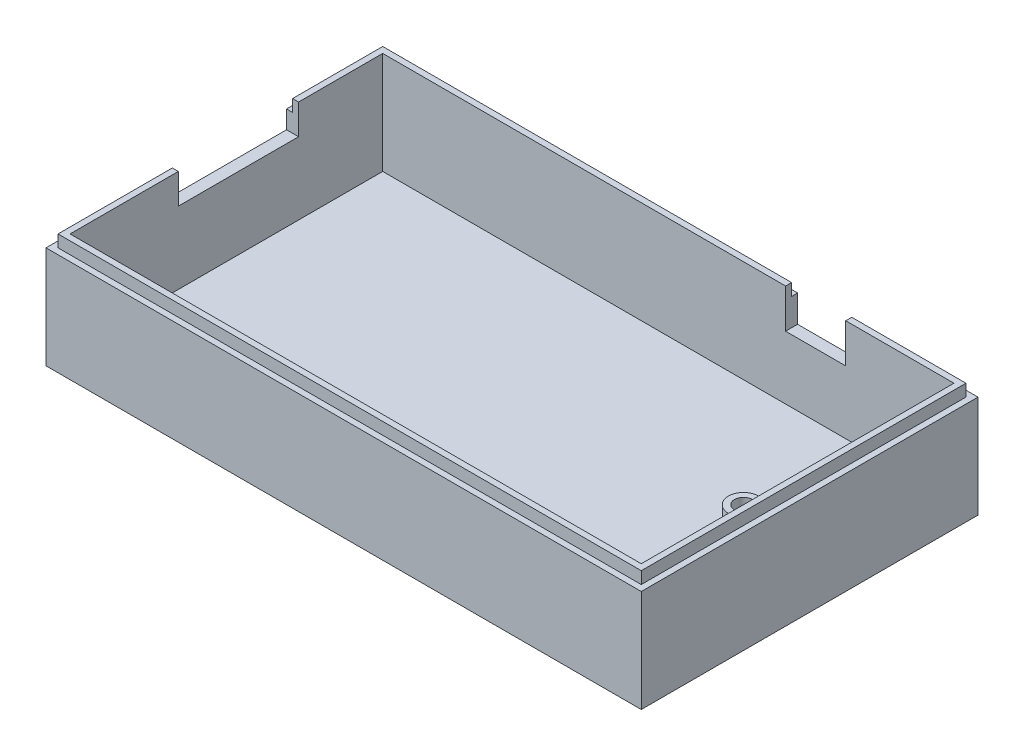
SolidWorks part; units mm, degrees
ref_plane "Front Plane" through (0, 0, 0) normal (0, 0, 1) x (1, 0, 0)
ref_plane "Top Plane" through (0, 0, 0) normal (0, 1, 0) x (1, 0, 0)
ref_plane "Right Plane" through (0, 0, 0) normal (1, 0, 0) x (0, 0, -1)
sketch "Sketch1" plane through (0, 0, 0) normal (0, 1, 0) x (1, 0, 0)
  line L1 (-49.5, 28) -> (49.5, 28)
  line L2 (-49.5, 28) -> (-49.5, -28)
  line L3 (-49.5, -28) -> (49.5, -28)
  line L4 (49.5, 28) -> (49.5, -28)
  line L5 (-49.5, 28) -> (49.5, -28) construction
  line L6 (-49.5, -28) -> (49.5, 28) construction
  line L7 (-47.5, 26) -> (47.5, 26)
  line L8 (-47.5, 26) -> (-47.5, -26)
  line L9 (-47.5, -26) -> (47.5, -26)
  line L10 (47.5, 26) -> (47.5, -26)
  line L11 (-47.5, 26) -> (47.5, -26) construction
  line L12 (-47.5, -26) -> (47.5, 26) construction
  line L13 (-48.5, 27) -> (48.5, 27)
  line L14 (-48.5, 27) -> (-48.5, -27)
  line L15 (-48.5, -27) -> (48.5, -27)
  line L16 (48.5, 27) -> (48.5, -27)
  line L17 (-48.5, 27) -> (48.5, -27) construction
  line L18 (-48.5, -27) -> (48.5, 27) construction
  circle A0 centre (38.5, 0) radius 2.5
  point P0 (0, 0)
  point P6 (0, 0)
  point P11 (38.5, 0)
  point P12 (0, 0)
  point P19 (44.5, 21)
  point P20 (-44.5, -21)
  dimension "D8" = 5
  dimension "D1" = 95
  dimension "D2" = 2
  dimension "D3" = 52
  dimension "D4" = 2
  dimension "D5" = 9
  dimension "D6" = 1
  dimension "D7" = 1
  dimension "D9" = 5
  dimension "D10" = 3
  dimension "D11" = 5
  dimension "D12" = 3
extrude "Boss-Extrude1" add sketch "Sketch1" along normal blind 8 contours A0 region at (38.5, 0, 0)
extrude "Boss-Extrude2" add sketch "Sketch1<3>" against normal blind 2 separate body contours L10 L7 L8 L9 A0 | L16 L13 L14 L15 L7 L10 L9 L8 | L4 L1 L2 L3 L13 L16 L15 L14 region at (0, 0, -27.8863) region at (-0.1536, 0, 0) region at (0, 0, -26.889)
sketch "Sketch1<3>" plane through (0, 0, 0) normal (0, 1, 0) x (1, 0, 0) same geometry as "Sketch1"
extrude "Boss-Extrude4" add sketch "Sketch1<5>" along normal blind 15 contours L16 L13 L14 L15 L7 L10 L9 L8 | L4 L1 L2 L3 L13 L16 L15 L14 region at (0, 0, -27.8863) region at (0, 0, -26.889)
sketch "Sketch1<5>" plane through (0, 0, 0) normal (0, 1, 0) x (1, 0, 0) same geometry as "Sketch1"
extrude "Boss-Extrude5" add sketch "Sketch1<6>" along normal blind 17 contours L16 L13 L14 L15 L7 L10 L9 L8 region at (0, 0, -26.889)
sketch "Sketch1<6>" plane through (0, 0, 0) normal (0, 1, 0) x (1, 0, 0) same geometry as "Sketch1"
hole_wizard "Ø3.0 (3) Diameter Hole1" positions "Sketch3" profile "Sketch4" hole size "Ø3.0" standard "ANSI Metric" end condition through all
sketch "Sketch3" plane through (0, 0, 0) normal (0, 1, 0) x (1, 0, 0)
  point P0 (-44.5, -21)
  point P3 (44.5, 21)
sketch "Sketch4" plane through (-44.5, 0, 21) normal (1, 0, 0) x (0, 0, 1)
  line L0 (0, 0) -> (0, 2)
  line L1 (0, 2) -> (1.5, 2)
  line L2 (1.5, 2) -> (1.5, 0)
  line L5 (1.5, 0) -> (0, 0)
  line L11 (0, -6.35) -> (0, 107.95) construction
  dimension "Thru Hole Dia." = 3
  dimension "Thru Hole Depth" = 2
hole_wizard "Ø3.0 (3) Diameter Hole2" positions "Sketch7" profile "Sketch8" hole size "Ø3.0" standard "ANSI Metric" end condition through all
sketch "Sketch7" plane through (0, 8, 0) normal (0, 1, 0) x (1, 0, 0)
  point P0 (38.5, 0)
sketch "Sketch8" plane through (38.5, 8, 0) normal (1, 0, 0) x (0, 0, 1)
  line L0 (0, 0) -> (0, 10)
  line L1 (0, 10) -> (1.5, 10)
  line L2 (1.5, 10) -> (1.5, 0)
  line L5 (1.5, 0) -> (0, 0)
  line L11 (0, -6.35) -> (0, 107.95) construction
  dimension "Thru Hole Dia." = 3
  dimension "Thru Hole Depth" = 10
sketch "Sketch9" plane through (-49.5, 0, 0) normal (-1, 0, 0) x (0, 0, 1)
  line L0 (-27, 17) -> (27, 17) construction
  line L1 (8, 17) -> (-12, 17)
  line L2 (8, 17) -> (8, 12)
  line L3 (8, 12) -> (-12, 12)
  line L4 (-12, 17) -> (-12, 12)
  line L5 (28, -2) -> (28, 15) construction
  dimension "D1" = 5
  dimension "D2" = 20
  dimension "D3" = 20
extrude "Cut-Extrude1" cut sketch "Sketch9" against normal up to next (2 mm away)
sketch "Sketch10" plane through (0, 0, -28) normal (0, 0, -1) x (-1, 0, 0)
  line L0 (48.5, 17) -> (-48.5, 17) construction
  line L1 (-29.5, 17) -> (-19.5, 17)
  line L2 (-29.5, 17) -> (-29.5, 10.4887)
  line L3 (-29.5, 10.4887) -> (-19.5, 10.4887)
  line L4 (-19.5, 17) -> (-19.5, 10.4887)
  line L5 (-49.5, -2) -> (-49.5, 15) construction
  point P8 (-29.5, 13.7443)
  dimension "D1" = 20
  dimension "D2" = 10
extrude "Cut-Extrude2" cut sketch "Sketch10" against normal up to next (2 mm away)
